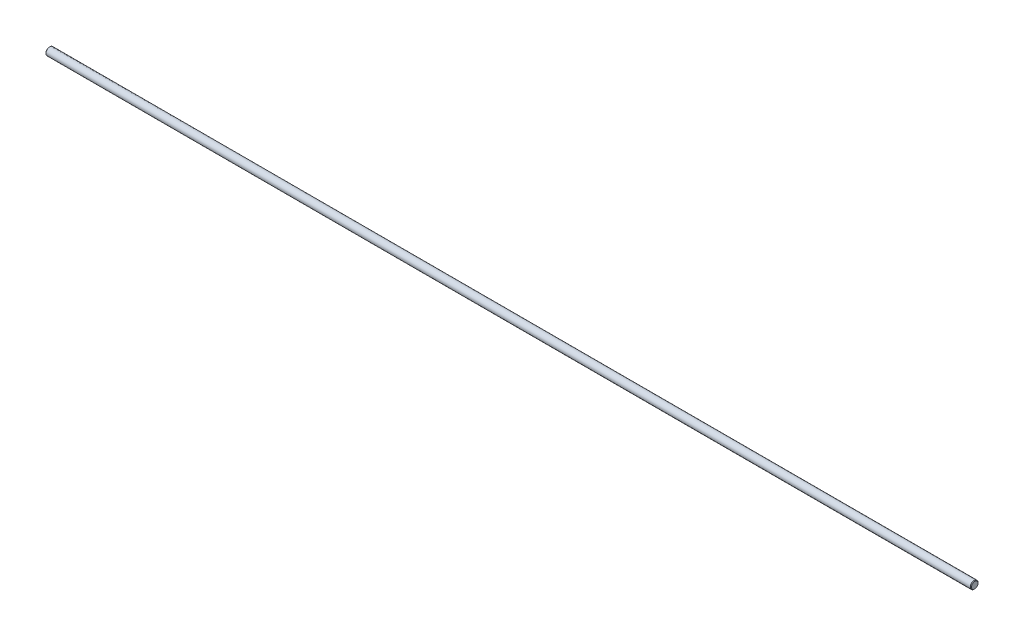
SolidWorks part; units mm, degrees
ref_plane "Front Plane" through (0, 0, 0) normal (0, 0, 1) x (1, 0, 0)
ref_plane "Top Plane" through (0, 0, 0) normal (0, 1, 0) x (1, 0, 0)
ref_plane "Right Plane" through (0, 0, 0) normal (1, 0, 0) x (0, 0, -1)
sketch "Sketch1" plane through (0, 0, 0) normal (0, 0, 1) x (1, 0, 0)
  line L0 (-38.1, 0) -> (38.1, 0) construction
  line L1 (38.1, 6.35) -> (38.1, -6.35) construction
  line L2 (-38.1, 6.35) -> (-38.1, -6.35) construction
  point P6 (33.655, -6.35)
  dimension "Thread Diameter" = 12.7
  dimension "Length" = 76.2
  dimension "D1" = 4.445
sketch "Sketch2" plane through (0, 0, 0) normal (1, 0, 0) x (0, 0, -1)
  circle A0 centre (0, 0) radius 6.35
extrude "Boss-Extrude1" add sketch "Sketch2" against normal blind 1524
sketch "Sketch3" plane through (0, 0, 0) normal (1, 0, 0) x (0, 0, -1)
  circle A1 centre (0, 0) radius 6.35
  circle A2 centre (0, 0) radius 6.35
  dimension "D1" = 0
curve "Helix/Spiral1" pitch 1.27 height 77.47 turns 61 parameters "Pitch"=1.27
chamfer "Chamfer1" distance 0.9525 angle 45 2 edges at (-1524, 0, -6.35) (0, 0, -6.35)
sketch "Sketch4" plane through (0, 0, 0) normal (0, 0, 1) x (1, 0, 0)
  line L0 (38.0206, 6.4875) -> (38.6556, 5.3876) construction
  line L1 (38.6556, 5.3876) -> (39.2906, 6.4875) construction
  line L2 (39.2906, 6.4875) -> (38.0206, 6.4875) construction
  line L3 (38.6556, 6.4875) -> (38.6556, 6.35) construction
  line L4 (38.6556, 5.3876) -> (38.6556, 5.5251) construction
  line L5 (38.5762, 5.5251) -> (38.735, 5.5251) construction
  line L6 (38.1, 6.35) -> (39.2112, 6.35) construction
  line L7 (38.5762, 5.5251) -> (38.0603, 6.4187)
  line L8 (38.5762, 5.5251) -> (38.735, 5.5251)
  line L9 (38.0603, 6.4187) -> (39.2509, 6.4187)
  line L10 (39.2509, 6.4187) -> (38.735, 5.5251)
  point P13 (38.6556, 6.4187)
  dimension "D2" = 0.1588
sweep "Cut-Sweep3" [suppressed] cut profiles "Sketch4" path "Helix/Spiral1"
equation "\"D3@Helix/Spiral1\" = \"Length@Sketch1\"+\"Pitch@Helix/Spiral1\""
equation "\"D1@Chamfer1\" = \"Pitch@Helix/Spiral1\"*.75"
equation "\"D1@Sketch4\" = \"Pitch@Helix/Spiral1\""
equation "\"D2@Sketch4\" = \"D1@Sketch4\"/8"
equation "\"D1@Sketch1\" = \"Pitch@Helix/Spiral1\"*3.50"
